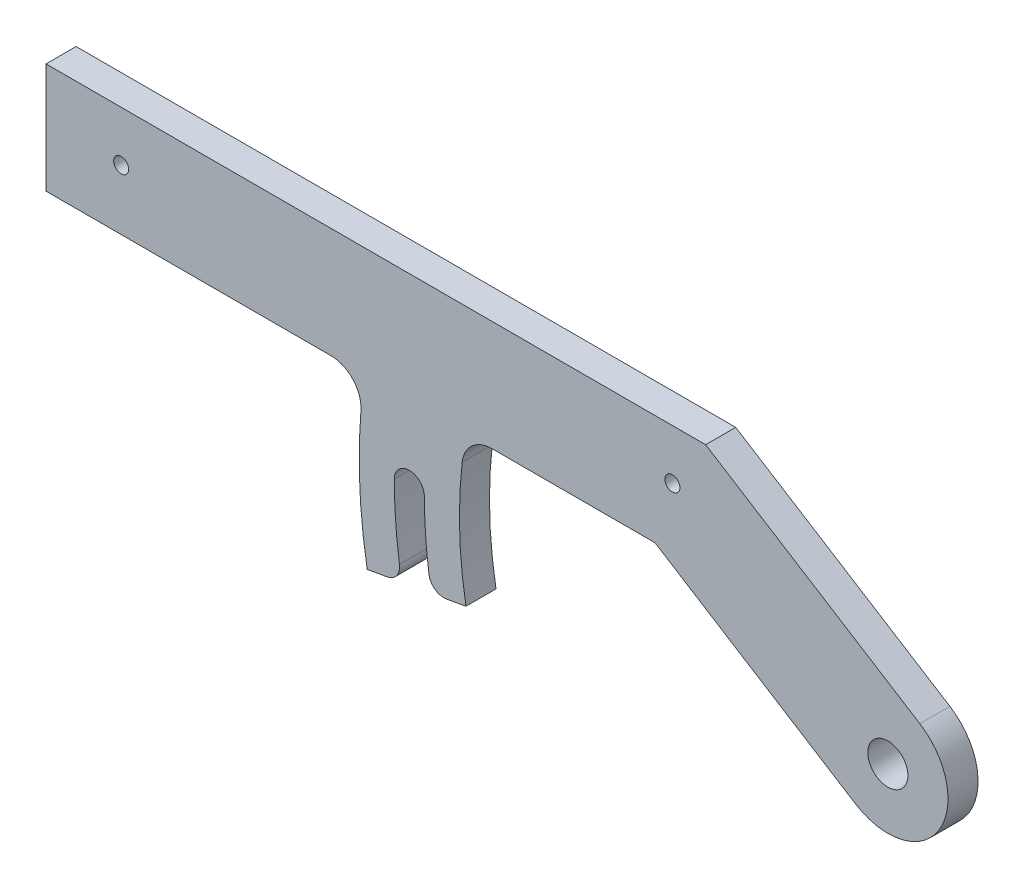
SolidWorks part; units mm, degrees
material "Balsa"
ref_plane "Plano frontal" through (0, 0, 0) normal (0, 0, 1) x (1, 0, 0)
ref_plane "Plano superior" through (0, 0, 0) normal (0, 1, 0) x (1, 0, 0)
ref_plane "Plano direito" through (0, 0, 0) normal (1, 0, 0) x (0, 0, -1)
sketch "Esboço1" plane through (0, 0, 0) normal (0, 0, 1) x (1, 0, 0)
  line L0 (40, 5) -> (83, -22) construction
  line L1 (76.6188, -32.1627) -> (36.5449, -7)
  line L2 (89.3812, -11.8373) -> (46.6403, 15)
  line L3 (46.6403, 15) -> (-85, 15)
  line L4 (-85, 15) -> (-85, -7)
  line L5 (-20.8972, -40.3199) -> (-16.9143, -39.6176)
  line L7 (4.0111, -7) -> (36.5449, -7)
  line L8 (-5.0908, -37.5328) -> (-1.2011, -36.8469)
  line L9 (38.0901, -22) -> (-46.1291, -22) construction
  line L13 (0, 8.6458) -> (0, -26.3908) construction
  line L18 (-85, -7) -> (-28.1362, -7)
  arc A0 (76.6188, -32.1627) -> (89.3812, -11.8373) centre (83, -22) ccw
  circle A1 centre (83, -22) radius 4
  arc A2 (-11.3146, -7) -> (-11.0491, -38.5834) centre (83, -22) ccw construction
  arc A3 (-15.5, -22) -> (-14.4667, -36.2298) centre (83, -22) ccw
  arc A4 (-9.5, -22) -> (-8.5819, -35) centre (83, -22) ccw
  arc A5 (-22.1558, -13.4843) -> (-20.8972, -40.3199) centre (83, -22) ccw
  circle A6 centre (-70, 5) radius 1.5
  circle A7 centre (40, 5) radius 1.5
  arc A8 (-1.9504, -12.3208) -> (-1.2011, -36.8469) centre (83, -22) ccw
  arc A9 (-1.4388, -8.5707) -> (-1.2011, -36.8469) centre (83, -22) ccw construction
  arc A10 (-8.3519, -7.4712) -> (-8.0947, -38.0625) centre (83, -22) ccw construction
  arc A11 (-21.1905, -5.4293) -> (-20.8972, -40.3199) centre (83, -22) ccw construction
  arc A12 (-14.2774, -6.5288) -> (-14.0036, -39.1043) centre (83, -22) ccw construction
  arc A13 (-15.5, -22) -> (-9.5, -22) centre (-12.5, -22) cw
  arc A16 (-14.4667, -36.2298) -> (-16.9143, -39.6176) centre (-17.4353, -36.6632) cw
  arc A17 (-8.5819, -35) -> (-5.0908, -37.5328) centre (-5.6117, -34.5784) ccw
  arc A18 (-22.1558, -13.4843) -> (-28.1362, -7) centre (-28.1362, -13) ccw
  arc A19 (-1.9504, -12.3208) -> (4.0111, -7) centre (4.0111, -13) cw
  point P0 (0, 0)
  point P43 (36.5449, -7)
  point P56 (-1.1739, -7)
  dimension "D13" = 3
  dimension "D15" = 10
  dimension "D5" = 3
  dimension "D3" = 8
  dimension "D4" = 12
  dimension "D10" = 95.5
  dimension "D17" = 83
  dimension "D20" = 3
  dimension "D21" = 6
  dimension "D2" = 10
  dimension "D6" = 15
  dimension "D7" = 12
  dimension "D8" = 85
  dimension "D9" = 70
  dimension "D11" = 40
  dimension "D12" = 5
  dimension "D14" = 10
  dimension "D16" = 10
extrude "Ressalto-extrusão1" add sketch "Esboço1" along normal blind 6
